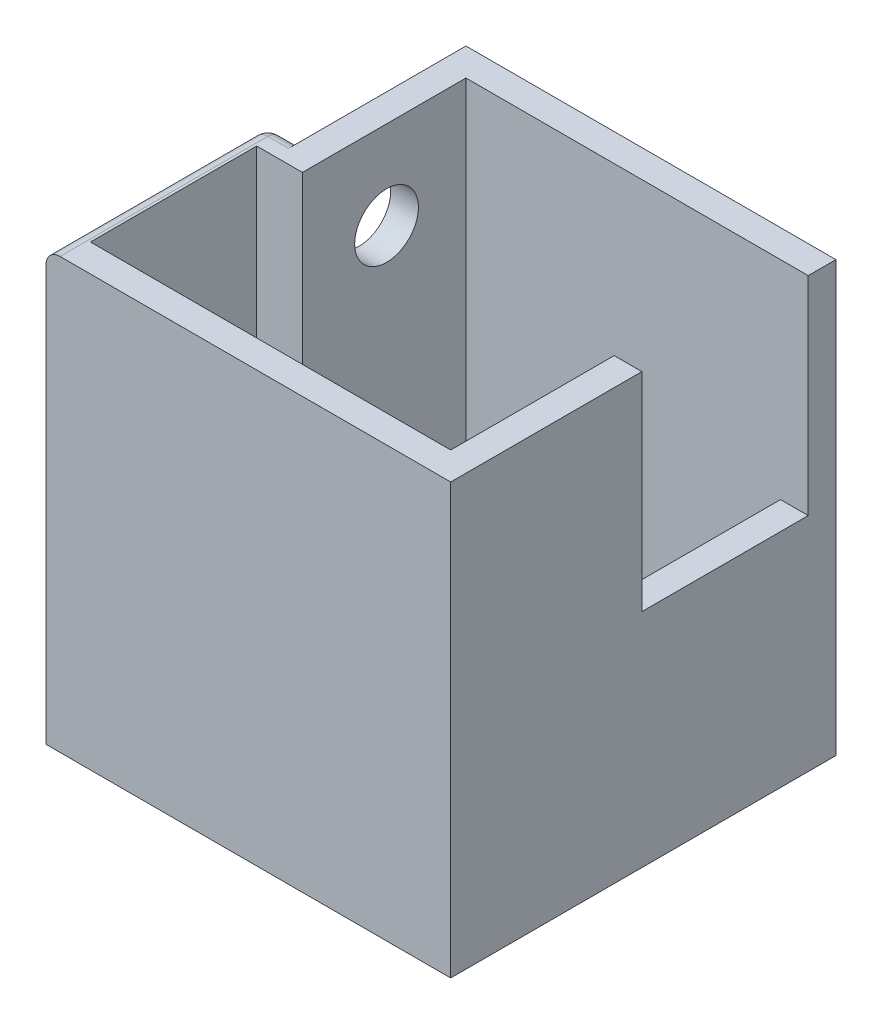
SolidWorks part; units mm, degrees
ref_plane "Plan de face" through (0, 0, 0) normal (0, 0, 1) x (1, 0, 0)
ref_plane "Plan de dessus" through (0, 0, 0) normal (0, 1, 0) x (1, 0, 0)
ref_plane "Plan de droite" through (0, 0, 0) normal (1, 0, 0) x (0, 0, -1)
sketch "Esquisse1" plane through (0, 0, 0) normal (0, 0, 1) x (1, 0, 0)
  line L1 (0, 0) -> (30, 0)
  line L2 (0, 0) -> (0, 31)
  line L3 (0, 31) -> (30, 31)
  line L4 (30, 0) -> (30, 31)
  dimension "D1" = 31
  dimension "D2" = 30
extrude "Boss.-Extru.1" add sketch "Esquisse1" along normal blind 27.8
shell "Coque1" thickness 2 removed face at (15, 31, 13.9)
sketch "Esquisse2" plane through (30, 0, 0) normal (1, 0, 0) x (0, 0, -1)
  line L0 (0, 31) -> (-2, 31) construction
  line L1 (-27.8, 31) -> (0, 31) construction
  line L3 (-2, 31) -> (-14, 31)
  line L4 (-2, 31) -> (-2, 16)
  line L5 (-2, 16) -> (-14, 16)
  line L6 (-14, 31) -> (-14, 16)
  dimension "D1" = 2
  dimension "D2" = 12
  dimension "D3" = 15
extrude "Enlèv. mat.-Extru.1" cut sketch "Esquisse2" against normal up to next
sketch "Esquisse3" plane through (0, 2, 0) normal (0, 1, 0) x (1, 0, 0)
  line L0 (0, -27.8) -> (0, 0) construction
  line L1 (4.1, -25.8) -> (19.1, -25.8)
  line L2 (4.1, -25.8) -> (4.1, -13.8)
  line L3 (4.1, -13.8) -> (19.1, -13.8)
  line L4 (19.1, -25.8) -> (19.1, -13.8)
  line L5 (0, -27.8) -> (30, -27.8) construction
  dimension "D1" = 15
  dimension "D2" = 12
  dimension "D3" = 4.1
  dimension "D4" = 2
extrude "Enlèv. mat.-Extru.2" cut sketch "Esquisse3" against normal up to next
sketch "Esquisse4" plane through (0, 2, 0) normal (0, 1, 0) x (1, 0, 0)
  line L0 (0, -27.8) -> (0, 0) construction
  line L1 (2, -13.8) -> (28, -13.8)
  line L2 (2, -13.8) -> (2, -2)
  line L3 (2, -2) -> (28, -2)
  line L4 (28, -13.8) -> (28, -2)
  dimension "D1" = 2
  dimension "D2" = 11.8
extrude "Boss.-Extru.2" add sketch "Esquisse4" along normal blind 1.5
sketch "Esquisse5" plane through (2, 0, 0) normal (1, 0, 0) x (0, 0, -1)
  line L1 (-13.8, 3.5) -> (-2, 3.5)
  line L2 (-13.8, 3.5) -> (-13.8, 31)
  line L3 (-13.8, 31) -> (-2, 31)
  line L4 (-2, 3.5) -> (-2, 31)
extrude "Boss.-Extru.3" add sketch "Esquisse5" along normal blind 3.3
sketch "Esquisse6" plane through (0, 2, 0) normal (0, 1, 0) x (1, 0, 0)
  line L1 (2, -13.8) -> (4.1, -13.8)
  line L2 (2, -13.8) -> (2, -25.8)
  line L3 (2, -25.8) -> (4.1, -25.8)
  line L4 (4.1, -13.8) -> (4.1, -25.8)
extrude "Boss.-Extru.4" add sketch "Esquisse6" along normal blind 6.3
sketch "Esquisse8" plane through (0, 0, 0) normal (-1, 0, 0) x (0, 0, 1)
  line L1 (0, 0) -> (11.8, 0)
  line L2 (0, 0) -> (0, 31)
  line L3 (0, 31) -> (11.8, 31)
  line L4 (11.8, 0) -> (11.8, 31)
  dimension "D1" = 11.8
extrude "Enlèv. mat.-Extru.3" cut sketch "Esquisse8" against normal blind 3.3
sketch "Esquisse10" plane through (3.3, 0, 0) normal (-1, 0, 0) x (0, 0, 1)
  line L0 (0, 0) -> (11.8, 0) construction
  circle A0 centre (7.73, 24.64) radius 2.3
  point P0 (7.73, 0)
  dimension "D2" = 4.6
  dimension "D1" = 7.73
  dimension "D3" = 24.64
extrude "Enlèv. mat.-Extru.4" cut sketch "Esquisse10" against normal up to next contours A0
sketch "Esquisse14" plane through (0, 31, 0) normal (0, 1, 0) x (1, 0, 0)
  line L0 (30, -27.8) -> (0, -27.8) construction
  line L1 (0, -11.8) -> (0.8, -11.8)
  line L2 (0, -11.8) -> (0, -27.8)
  line L3 (0, -27.8) -> (0.8, -27.8)
  line L4 (0.8, -11.8) -> (0.8, -27.8)
  dimension "D1" = 0.8
extrude "Enlèv. mat.-Extru.5" cut sketch "Esquisse14" against normal up to next
fillet "Congé2" radius 1 1 edges at (2.05, 31, 11.8)
fillet "Congé3" radius 1 3 edges at (0.8, 15, 11.8) (0.8, 30.7071, 12.0929) (0.8, 31, 20.3)
sketch "Esquisse15" plane through (0.8, 0, 0) normal (-1, 0, 0) x (0, 0, 1)
  line L0 (12.8, 30) -> (12.8, 0) construction
  line L1 (16.3, 20.65) -> (24.3, 20.65)
  line L2 (16.3, 20.65) -> (16.3, 18.55)
  line L3 (16.3, 18.55) -> (24.3, 18.55)
  line L4 (24.3, 20.65) -> (24.3, 18.55)
  line L5 (21.5, 20.2) -> (17.9, 20.2) construction
  dimension "D1" = 2.1
  dimension "D2" = 8
  dimension "D3" = 3.5
  dimension "D4" = 0.45
extrude "Enlèv. mat.-Extru.6" cut sketch "Esquisse15" against normal up to next
